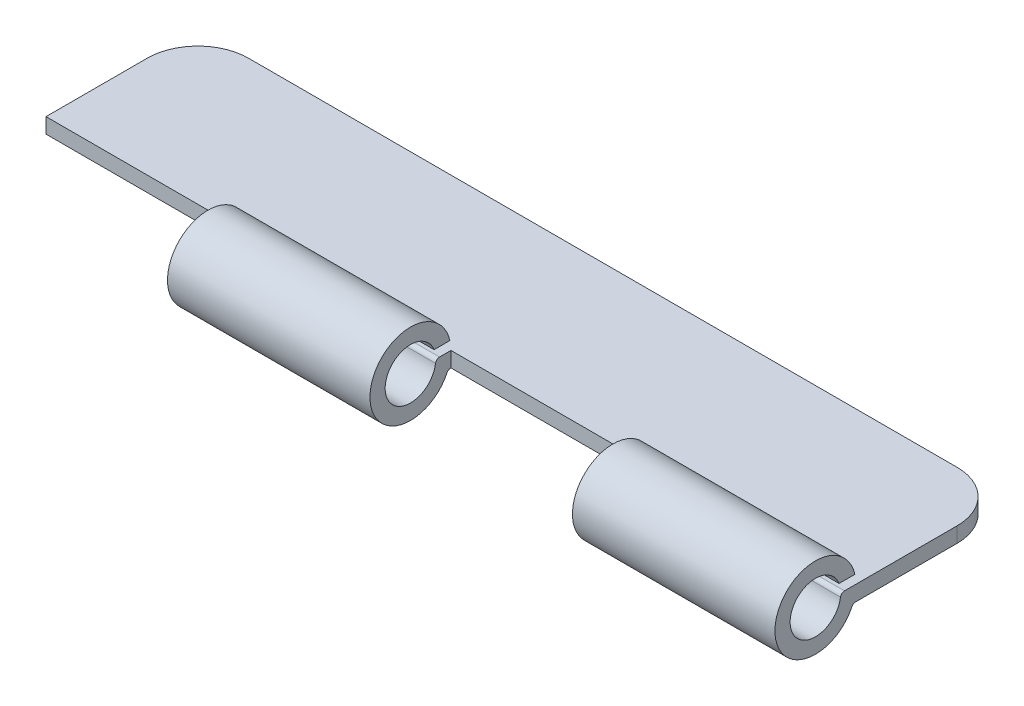
SolidWorks part; units mm, degrees
material "Brass"
ref_plane "Front Plane" through (0, 0, 0) normal (0, 0, 1) x (1, 0, 0)
ref_plane "Top Plane" through (0, 0, 0) normal (0, 1, 0) x (1, 0, 0)
ref_plane "Right Plane" through (0, 0, 0) normal (1, 0, 0) x (0, 0, -1)
sketch "Sketch1" plane through (0, 0, 0) normal (0, 1, 0) x (1, 0, 0)
  line L1 (-40, -17.5) -> (40, -17.5)
  line L2 (-40, -17.5) -> (-40, -7.5)
  line L3 (-35, -2.5) -> (35, -2.5)
  line L4 (40, -17.5) -> (40, -7.5)
  line L5 (-40, -17.5) -> (40, 17.5) construction
  line L6 (-40, 17.5) -> (40, -17.5) construction
  arc A0 (35, -2.5) -> (40, -7.5) centre (35, -7.5) cw
  arc A1 (-40, -7.5) -> (-35, -2.5) centre (-35, -7.5) cw
  point P0 (0, 0)
  dimension "D1" = 5
  dimension "D2" = 10
extrude "Boss-Extrude1" add sketch "Sketch1" along normal blind 1.5
sketch "Sketch2" plane through (40, 0, 0) normal (1, 0, 0) x (0, 0, -1)
  line L0 (-17.6018, 2.3968) -> (-19.1664, 2.3968)
  line L1 (-17.5, 1.5) -> (-18.6277, 1.5)
  line L2 (-17.5314, 0) -> (-17.5, 0)
  line L3 (-17.5, 0) -> (-17.5, 1.5)
  arc A0 (-17.6018, 2.3968) -> (-17.8922, -0.2273) centre (-21.5, 1.5) ccw
  arc A1 (-19.1664, 2.3968) -> (-19.0239, 1.1552) centre (-21.5, 1.5) ccw
  arc A2 (-17.5314, 0) -> (-17.8922, -0.2273) centre (-17.5314, -0.4) ccw
  arc A3 (-18.6277, 1.5) -> (-19.0239, 1.1552) centre (-18.6277, 1.1) ccw
  dimension "D1" = 8
  dimension "D2" = 5
  dimension "D3" = 0.4
extrude "Boss-Extrude2" add sketch "Sketch2" against normal blind 20
pattern_linear "LPattern1" count 2 spacing 40 along (-1, 0, 0) of "Boss-Extrude2"
